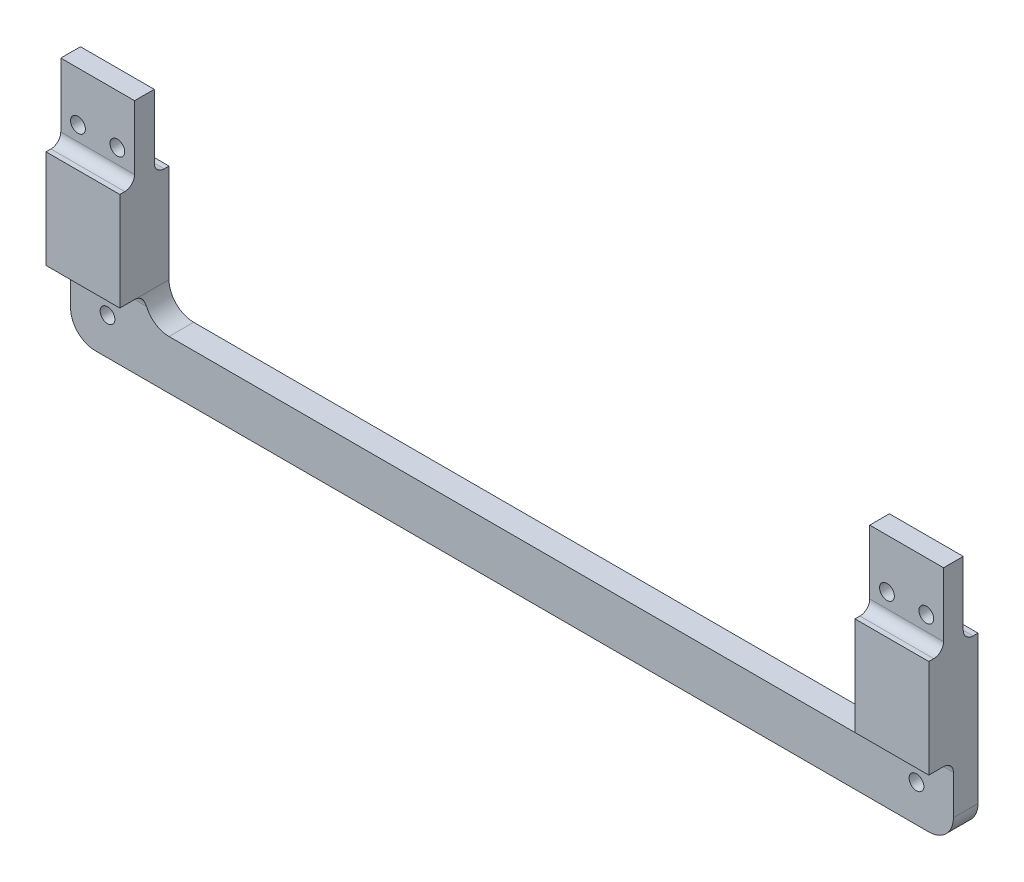
SolidWorks part; units mm, degrees
material "PUR"
ref_plane "Front Plane" through (0, 0, 0) normal (0, 0, 1) x (1, 0, 0)
ref_plane "Top Plane" through (0, 0, 0) normal (0, 1, 0) x (1, 0, 0)
ref_plane "Right Plane" through (0, 0, 0) normal (1, 0, 0) x (0, 0, -1)
sketch "Sketch1" plane through (0, 0, 0) normal (0, 0, 1) x (1, 0, 0)
  line L1 (-15.7614, 26.1548) -> (-0.7614, 26.1548)
  line L2 (-15.7614, 26.1548) -> (-15.7614, -23.8452)
  line L3 (-15.7614, -23.8452) -> (-0.7614, -23.8452)
  line L4 (-0.7614, 26.1548) -> (-0.7614, -23.8452)
  dimension "D1" = 15
  dimension "D2" = 50
extrude "Boss-Extrude1" add sketch "Sketch1" along normal blind 10
sketch "Sketch2" plane through (-0.7614, 0, 0) normal (1, 0, 0) x (0, 0, -1)
  line L1 (0, 26.1548) -> (-3, 26.1548)
  line L2 (0, 26.1548) -> (0, 11.1548)
  line L3 (0, 11.1548) -> (-3, 11.1548)
  line L4 (-3, 26.1548) -> (-3, 11.1548)
  line L5 (-10, 26.1548) -> (-7, 26.1548)
  line L6 (-10, 26.1548) -> (-10, 11.1548)
  line L7 (-10, 11.1548) -> (-7, 11.1548)
  line L8 (-7, 26.1548) -> (-7, 11.1548)
  dimension "D1" = 3
  dimension "D2" = 15
  dimension "D3" = 3
  dimension "D4" = 15
extrude "Cut-Extrude1" cut sketch "Sketch2" against normal blind 20
sketch "Sketch3" plane through (0, 0, 3) normal (0, 0, -1) x (-1, 0, 0)
  line L0 (15.7614, 11.1548) -> (0.7614, 11.1548) construction
  line L1 (0.7614, 26.1548) -> (0.7614, 11.1548) construction
  line L2 (15.7614, 26.1548) -> (15.7614, 11.1548) construction
  circle A0 centre (4.2614, 16.1548) radius 1.5
  circle A1 centre (12.2614, 16.1548) radius 1.5
  dimension "D1" = 5
  dimension "D3" = 3
  dimension "D4" = 3.5
  dimension "D5" = 5
  dimension "D6" = 3
  dimension "D2" = 3.5
extrude "Cut-Extrude2" cut sketch "Sketch3" against normal blind 20
sketch "Sketch4" plane through (-0.7614, 0, 0) normal (1, 0, 0) x (0, 0, -1)
  line L1 (-10, -23.8452) -> (-5, -23.8452)
  line L2 (-10, -23.8452) -> (-10, -8.8452)
  line L3 (-10, -8.8452) -> (-5, -8.8452)
  line L4 (-5, -23.8452) -> (-5, -8.8452)
  dimension "D1" = 5
  dimension "D2" = 15
extrude "Cut-Extrude3" cut sketch "Sketch4" against normal blind 20
sketch "Sketch5" plane through (0, 0, 5) normal (0, 0, 1) x (1, 0, 0)
  line L1 (-15.7614, -23.8452) -> (-0.7614, -23.8452) construction
  line L2 (-8.2614, -23.8452) -> (-8.2614, -77.9899) construction
  circle A0 centre (-8.2614, -16.3452) radius 1.5
  dimension "D1" = 3
  dimension "D2" = 7.5
extrude "Cut-Extrude4" cut sketch "Sketch5" against normal up to next
fillet "Fillet1" radius 2 3 edges at (-8.2614, -8.8452, 5) (-8.2614, 11.1548, 3) (-8.2614, 11.1548, 7)
ref_plane "Plane1" through (-90.4614, 0, 0) normal (-1, 0, 0) x (0, 0, 1)
sketch "Sketch6" plane through (-15.7614, 0, 0) normal (-1, 0, 0) x (0, 0, 1)
  line L0 (5, -23.8452) -> (0, -23.8452) construction
  line L1 (5, -23.8452) -> (0, -23.8452)
  line L2 (5, -23.8452) -> (5, -13.8452)
  line L3 (5, -13.8452) -> (0, -13.8452)
  line L4 (0, -23.8452) -> (0, -13.8452)
  line L5 (0, 11.1548) -> (0, -23.8452) construction
  dimension "D1" = 5
  dimension "D2" = 10
extrude "Boss-Extrude2" add sketch "Sketch6" along normal blind 149.4
mirror "Mirror5" about plane through (-90.4614, 0, 0) normal (-1, 0, 0) of "Boss-Extrude1", "Cut-Extrude1", "Cut-Extrude2", "Cut-Extrude3", "Cut-Extrude4", "Fillet1"
fillet "Fillet2" radius 5 4 edges at (-180.1614, -23.8452, 2.5) (-0.7614, -23.8452, 2.5) (-165.1614, -13.8452, 2.5) (-15.7614, -13.8452, 2.5)
